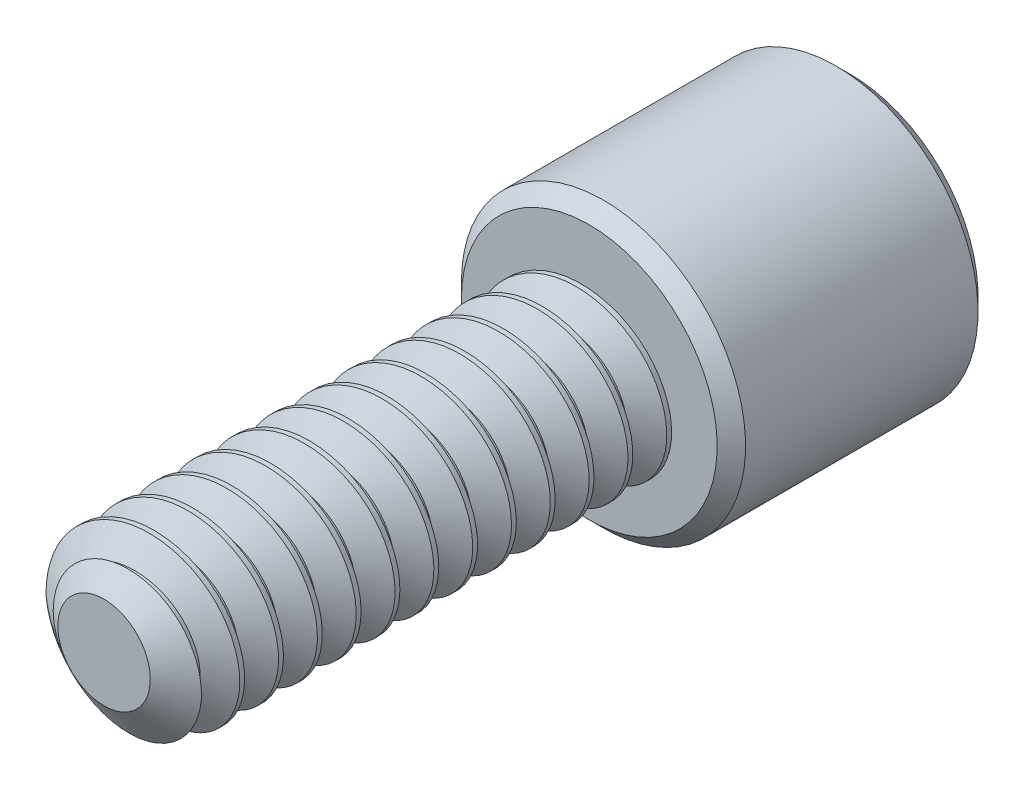
SolidWorks part; units mm, degrees
ref_plane "Front Plane" through (0, 0, 0) normal (0, 0, 1) x (1, 0, 0)
ref_plane "Top Plane" through (0, 0, 0) normal (0, 1, 0) x (1, 0, 0)
ref_plane "Right Plane" through (0, 0, 0) normal (1, 0, 0) x (0, 0, -1)
sketch "Sketch1" plane through (0, 0, 0) normal (0, 0, 1) x (1, 0, 0)
  circle A0 centre (0, 0) radius 1.4224
  dimension "OD" = 2.8448
extrude "Extrude1" add sketch "Sketch1" against normal blind 7.9375
sketch "Sketch2" plane through (0, 0, 0) normal (0, 0, 1) x (1, 0, 0)
  circle A0 centre (0, 0) radius 1.4224 construction
  circle A1 centre (0, 0) radius 1.4224
curve "Helix/Spiral1" pitch 0.635 height 8.5725 radius 1.4224 centre (0, 0, 0) axis (0, 0, -1) start towards (0, 1, 0) parameters "pitch"=0.635
sketch "Sketch3" plane through (0, 0, 0) normal (1, 0, 0) x (0, 0, -1)
  line L0 (-0.5556, 1.4224) -> (-0.3175, 1.01)
  line L1 (-0.3175, 1.01) -> (-0.2381, 1.01)
  line L2 (-0.2381, 1.01) -> (0, 1.4224)
  line L3 (-0.5556, 1.4224) -> (0, 1.4224)
  line L4 (-0.2778, 1.4224) -> (-0.2778, 1.01) construction
  line L5 (-0.4366, 1.2162) -> (-0.1191, 1.2162) construction
  line L6 (0, 1.4224) -> (0, -1.4224) construction
  dimension "D1" = 0.0794
  dimension "D2" = 0.3175
  dimension "D3" = 60
sweep "Cut-Sweep1" cut profiles "Sketch3" path "Helix/Spiral1" align with end faces yes
sketch "Sketch4" plane through (0, 0, 0) normal (1, 0, 0) x (0, 0, -1)
  line L0 (0.4666, 1.4224) -> (0, 0.756)
  line L1 (0, 0.756) -> (0, 1.4224)
  line L2 (0.4666, 1.4224) -> (0, 1.4224)
  line L3 (-0.5556, 1.4224) -> (0, 1.4224) construction
  line L4 (0, 0) -> (7.0209, 0) construction
  dimension "D1" = 55
  dimension "D2" = 0.254
revolve "Cut-Revolve1" cut sketch "Sketch4" angle 360 about L4
sketch "Sketch6" plane through (0, 0, -7.9375) normal (0, 0, -1) x (-1, 0, 0)
  circle A0 centre (0, 0) radius 2.3241
  dimension "head dia" = 4.6482
extrude "Extrude2" add sketch "Sketch6" along normal blind 4.2672
sketch "Sketch7" plane through (0, 0, -12.2047) normal (0, 0, -1) x (-1, 0, 0)
  line L1 (0, 1.3748) -> (-1.1906, 0.6874)
  line L2 (-1.1906, 0.6874) -> (-1.1906, -0.6874)
  line L3 (-1.1906, -0.6874) -> (0, -1.3748)
  line L4 (0, -1.3748) -> (1.1906, -0.6874)
  line L5 (1.1906, -0.6874) -> (1.1906, 0.6874)
  line L6 (1.1906, 0.6874) -> (0, 1.3748)
  circle A0 centre (0, 0) radius 1.1906 construction
  dimension "hex dia" = 2.3813
extrude "Cut-Extrude1" cut sketch "Sketch7" against normal blind 1.7859
sketch "Sketch8" plane through (0, 0, -12.2047) normal (0, 0, -1) x (-1, 0, 0)
  circle A0 centre (0, 0) radius 1.3748
extrude "Cut-Extrude2" cut sketch "Sketch8" against normal through all draft 45
chamfer "Chamfer1" distance 0.2324 angle 45 2 edges at (-2.3241, 0, -12.2047) (-2.3241, 0, -7.9375)
sketch "Sketch10" plane through (0, 0, -7.9375) normal (0, 0, 1) x (1, 0, 0)
  circle A1 centre (0, 0) radius 1.4224
  circle A2 centre (0, 0) radius 1.4224
  dimension "D1" = 0
ref_plane "Plane1" through (0, 0, -25.4) normal (0, 0, 1) x (1, 0, 0)
extrude "partial thread" [suppressed] add sketch "Sketch10" along normal up to surface (12.7 mm away) separate body up to plane "Plane1"
chamfer "Chamfer2" [suppressed] distance 0.0569 angle 45
combine bodies "Combine1" [suppressed] operation type add bodies to combine 107 108
sketch "Sketch9" plane through (0, 0, 0) normal (1, 0, 0) x (0, 0, -1)
  line L0 (0, 1.4224) -> (0, -1.4224) construction
  line L1 (1.5875, 1.4224) -> (1.5875, -1.4224) construction
  dimension "D1" = 1.5875
equation "\"D3@Helix/Spiral1\" = \"screw length@Extrude1\"+\"pitch@Helix/Spiral1\""
equation "\"D1@Sketch3\" = \"pitch@Helix/Spiral1\"*.125"
equation "\"D2@Sketch3\" = \"pitch@Helix/Spiral1\"*.5"
equation "\"D1@Cut-Extrude1\" = \"hex dia@Sketch7\"*.75"
equation "\"D1@Chamfer1\" = \"head dia@Sketch6\"*.05"
equation "\"D1@Sketch9\" = \"pitch@Helix/Spiral1\"*2.5"
equation "\"D1@Chamfer2\"=\"OD@Sketch1\"*.02"
